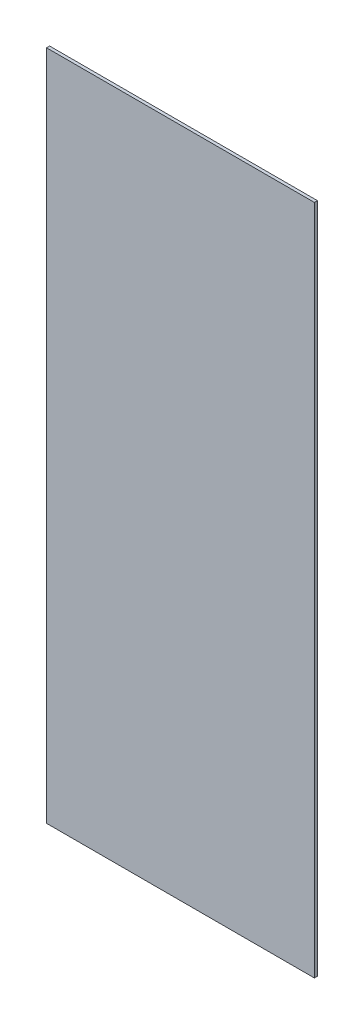
SolidWorks part; units mm, degrees
ref_plane "Спереди" through (0, 0, 0) normal (0, 0, 1) x (1, 0, 0)
ref_plane "Сверху" through (0, 0, 0) normal (0, 1, 0) x (1, 0, 0)
ref_plane "Справа" through (0, 0, 0) normal (1, 0, 0) x (0, 0, -1)
other "Configuration Table"
sketch "Эскиз1" plane through (0, 0, 0) normal (0, 0, 1) x (1, 0, 0)
  line L0 (0, -11) -> (0, -441) construction
  line L1 (524, 431) -> (0, 431)
  line L2 (524, 431) -> (524, -883)
  line L3 (524, -883) -> (0, -883)
  line L4 (0, 431) -> (0, -883)
  line L5 (524, 425) -> (524, -5) construction
  line L6 (0, 431) -> (518, 431) construction
  line L10 (518, -877) -> (524, -877) construction
  dimension "D1" = 6
extrude "Бобышка-Вытянуть1" add sketch "Эскиз1" against normal blind 6
equation "\"Толщина стенки\" = 6"
equation "\"D1@Эскиз1\"=\"Толщина стенки\""
equation "\"Ширина груза\"= 420"
equation "\"Глубина груза\"= 490"
equation "\"Высота груза\"= 297"
equation "\"Ширина ячейки\"= \"Ширина груза\" + 10"
equation "\"Глубина ячейки\"= \"Глубина груза\" + 10"
equation "\"Высота ячейки\"= \"Высота груза\" + 10 + 13"
equation "\"Колво ячеек ширина\"= 2"
equation "\"Колво ячеек высота\"= 2"
equation "\"Крепление дверцы\"= 5 "
equation "\"Ширина рейки\"= \"Толщина шестерни\""
equation "\"Высота рейки\"= 20"
equation "\"Высота пола\"= \"Толщина стенки\" * 2"
equation "\"Колво полозьев\"= 5"
equation "\"Отступ рейки\"= 20"
equation "\"Глубина каретки\"= \"Глубина ячейки\" + 30 + \"Мотор Y высота корпуса\" + 20"
equation "\"Длинна рейки\"= ( \"Ширина ячейки\" + \"Толщина стенки\" + \"Крепление дверцы\" ) * \"Колво ячеек ширина\" + \"Ширина ячейки выгрузки\" * \"Колво выгрузки\" + \"Толщина стенки\""
equation "\"Отступ шпильки\"= 26"
equation "\"Диаметр шпильки\"= 5"
equation "\"Длинна шпильки\"= ( \"Высота ячейки\" + \"Толщина стенки\" + \"Высота пола\" ) * \"Колво ячеек высота\" + ( \"Толщина стенки\" + \"Отступ рейки\" ) * 2 "
equation "\"Ширина пластины\"= 50  "
equation "\"Высота зона выгрузки\"= \"Высота ячейки\" * 2 + \"Толщина стенки\" * 2"
equation "\"Колво выгрузки\"= 1"
equation "\"Ширина ячейки выгрузки\"= \"Ширина ячейки\" + \"Толщина стенки\" + \"Отступ крепления мотора фиксации\"*2"
equation "\"Отступ крепления мотора фиксации\" = 30"
equation "\"Мотор X ширина корпуса\"= 42.3"
equation "\"Мотор X высота корпуса\"= 42.3"
equation "\"Мотор X длина корпуса\"= 40"
equation "\"Мотор X вылет вала\"= 19.8"
equation "\"Мотор Y ширина корпуса\"= 42.3"
equation "\"Мотор Y высота корпуса\"= 42.3"
equation "\"Мотор Y длина корпуса\"= 48"
equation "\"Мотор Y вылет вала\"= 30"
equation "\"Мотор Z ширина корпуса\"= 42"
equation "\"Мотор Z высота корпуса\"= 42"
equation "\"Мотор Z длина корпуса\"= 40"
equation "\"Мотор Z вылет вала\"= 23"
equation "\"Мотор диаметр вала ПРЕДВ\"= 5"
equation "\"Мотор шаг крепления ПРЕДВ\"= 31"
equation "\"Мотор диаметр отверстий ПРЕДВ\"= 3"
equation "\"Мотор глубина отверстий ПРЕДВ\"= 4.5"
equation "\"Мотор диаметр буртика ПРЕДВ\"= 22"
equation "\"Мотор высота буртика ПРЕДВ\"= 2"
equation "\"Мотор диаметр шкива ПРЕДВ\"= 16"
equation "\"Мотор длина шкива ПРЕДВ\"= 12"
equation "\"Мотор отступ шкива ПРЕДВ\"= 5"
equation "\"Мотор X шаг градусов\"= 1.8"
equation "\"Мотор Y шаг градусов\"= 1.8"
equation "\"Мотор Z шаг градусов\"= 1.8"
equation "\"Мотор Y диаметр ротора\"= 25.78"
equation "\"Толщина шестерни\"= 10"
equation "\"D1@Бобышка-Вытянуть1\"=\"Толщина стенки\""
